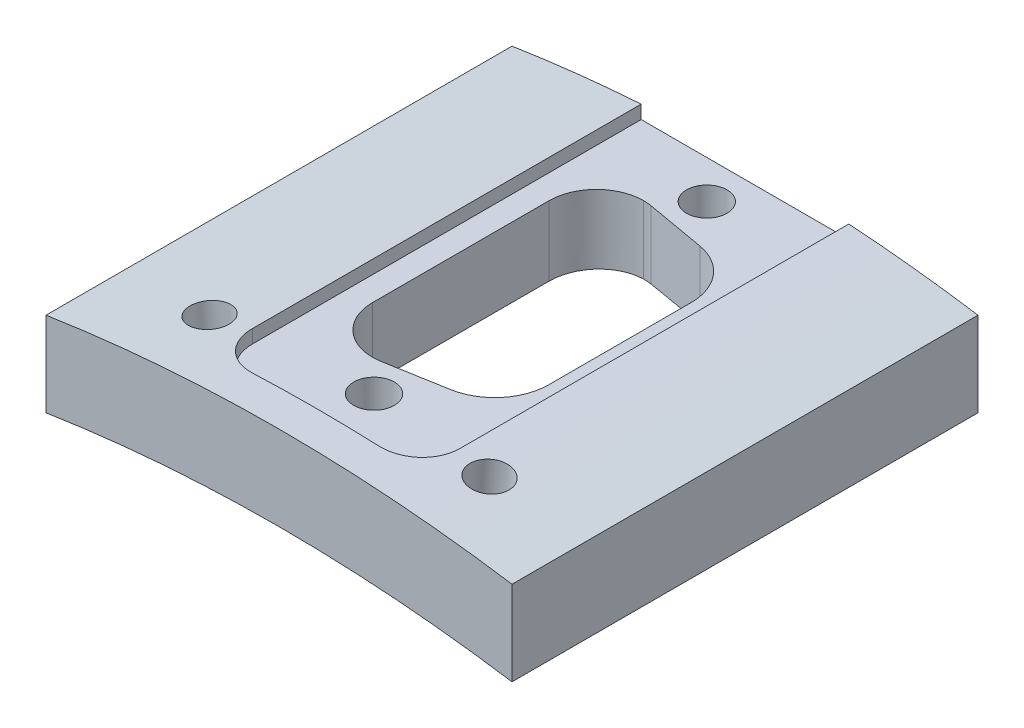
SolidWorks part; units mm, degrees
ref_plane "Front Plane" through (0, 0, 0) normal (0, 0, 1) x (1, 0, 0)
ref_plane "Top Plane" through (0, 0, 0) normal (0, 1, 0) x (1, 0, 0)
ref_plane "Right Plane" through (0, 0, 0) normal (1, 0, 0) x (0, 0, -1)
sketch "Sketch1" plane through (0, 0, 0) normal (0, 0, 1) x (1, 0, 0)
  line L1 (0, 0) -> (-35, 0)
  line L2 (0, 0) -> (0, -12.7)
  line L3 (0, -12.7) -> (-35, -12.7)
  line L4 (-35, 0) -> (-35, -12.7)
  arc A0 (-35, -12.7) -> (0, -12.7) centre (-17.5, -125.7809) cw
  dimension "D1" = 35
  dimension "D3" = 114.427
  dimension "D2" = 12.7
extrude "Boss-Extrude1" add sketch "Sketch1" along normal blind 35 contours L4 A0 L2 L1 region at (-17.5, -5.9076, 0)
ref_plane "Plane2" through (0, -11.3539, 0) normal (0, -1, 0) x (1, 0, 0)
ref_plane "Plane3" through (-1.0808, -12.3533, 0) normal (-0.0872, -0.9962, 0) x (0.9962, -0.0872, 0)
ref_plane "Plane4" through (0.8149, -9.3145, 0) normal (0.0872, -0.9962, 0) x (0.9962, 0.0872, 0)
sketch "Sketch3" plane through (0, 0, 35) normal (0, 0, 1) x (1, 0, 0)
  line L0 (-17.5, -125.6524) -> (-17.5, 0) construction
  line L1 (0, 0) -> (-35, 0) construction
  line L2 (-17.5, -125.6524) -> (-6.5068, 0) construction
  line L3 (-17.5, -125.6524) -> (-28.4932, 0) construction
  circle A0 centre (-17.5, -125.6524) radius 114.3
  dimension "D1" = 228.6
  dimension "D2" = 5
  dimension "D3" = 5
sketch "Sketch6" plane through (-1.0808, -12.3533, 0) normal (-0.0872, -0.9962, 0) x (0.9962, -0.0872, 0)
  line L0 (-6.4821, 35) -> (-6.4821, 0) construction
  line L1 (107.8179, 35) -> (-120.7821, 35) construction
  line L2 (1.1069, 0) -> (-33.7599, 0) construction
  circle A0 centre (-6.4821, 29.7028) radius 1.4732
  dimension "D1" = 2.9464
  dimension "D2" = 29.7028
extrude "Cut-Extrude4" cut sketch "Sketch6" against normal through all and the other way through all
sketch "Sketch7" plane through (0.8149, -9.3145, 0) normal (0.0872, -0.9962, 0) x (0.9962, 0.0872, 0)
  line L0 (-28.3847, 35) -> (-28.3847, 0) construction
  line L1 (85.9153, 35) -> (-142.6847, 35) construction
  line L2 (-1.1069, 0) -> (-35.9737, 0) construction
  circle A0 centre (-28.3847, 29.7028) radius 1.4732
  dimension "D1" = 2.9464
  dimension "D2" = 29.7028
extrude "Cut-Extrude5" cut sketch "Sketch7" against normal through all and the other way through all
sketch "Sketch8" plane through (0, 0, 0) normal (0, 0, -1) x (-1, 0, 0)
  line L0 (0, -6.35) -> (35, -6.35) construction
  line L3 (35, -12.7) -> (35, 0)
  line L4 (35, 0) -> (0, 0)
  line L5 (0, 0) -> (0, -12.7)
  line L6 (35, -12.7) -> (35, 0)
  line L7 (35, 0) -> (0, 0)
  line L8 (0, 0) -> (0, -12.7)
  arc A0 (0, -6.35) -> (35, -6.35) centre (17.5, -119.4309) cw
  arc A1 (35, -12.7) -> (0, -12.7) centre (17.5, -125.7809) ccw
  arc A2 (35, -12.7) -> (0, -12.7) centre (17.5, -125.7809) ccw
  line M6 (35, 0) -> (0, 0)
  line M7 (0, 0) -> (0, -12.7)
  dimension "D3" = 114.427
  dimension "D2" = 6.35
  dimension "D1" = 0
extrude "Cut-Extrude6" cut sketch "Sketch8" against normal through all contours A0 L6 M7 M6 region at (-17.5, -2.7405, 0)
sketch "Sketch9" plane through (0, 0, 0) normal (0, 0, -1) x (-1, 0, 0)
  line L0 (17.5, -11.3539) -> (17.5, -5.0039) construction
  line L2 (35, -12.7) -> (35, -6.35)
  line L3 (0, -6.35) -> (0, -12.7)
  line L4 (35, -12.7) -> (35, -6.35)
  line L5 (0, -6.35) -> (0, -12.7)
  arc A2 (35, -6.35) -> (0, -6.35) centre (17.5, -119.4309) ccw
  arc A3 (35, -12.7) -> (0, -12.7) centre (17.5, -125.7809) ccw
  arc A4 (35, -6.35) -> (0, -6.35) centre (17.5, -119.4309) ccw
  arc A5 (35, -12.7) -> (0, -12.7) centre (17.5, -125.7809) ccw
  dimension "D1" = 0
ref_plane "Plane5" through (-17.5, -5.0039, 0) normal (0, 1, 0) x (-1, 0, 0)
sketch "Sketch10" plane through (-17.5, -5.0039, 0) normal (0, 1, 0) x (-1, 0, 0)
  line L0 (-17.5, 27.8638) -> (17.5, 27.8638) construction
  line L1 (-17.5, 35) -> (-17.5, 0) construction
  line L2 (17.5, 35) -> (17.5, 0) construction
  line L3 (-17.5, 0) -> (17.5, 0) construction
  line L5 (0, 0) -> (0, 27.8638) construction
  line L7 (-17.5, 0) -> (17.5, 0) construction
  line B0 (6.2738, 1.524) -> (6.2738, 29.21)
  line B1 (4.7498, 30.734) -> (-4.7498, 30.734)
  line B2 (-6.2738, 29.21) -> (-6.2738, 1.524)
  line B3 (-4.7498, 0) -> (4.7498, 0)
  line B4 (1.8082, 5.2379) -> (-2.6234, 6.0193)
  line B5 (-5.9817, 10.0215) -> (-5.9817, 20.7125)
  line B6 (-2.6234, 24.7147) -> (1.8082, 25.4961)
  line B7 (5.9817, 21.9942) -> (5.9817, 8.7398)
  circle B8 centre (0, 27.8638) radius 1.524
  arc B9 (4.7498, 0) -> (6.2738, 1.524) centre (4.7498, 1.524) ccw
  arc B10 (6.2738, 29.21) -> (4.7498, 30.734) centre (4.7498, 29.21) ccw
  arc B11 (-4.7498, 30.734) -> (-6.2738, 29.21) centre (-4.7498, 29.21) ccw
  arc B12 (-6.2738, 1.524) -> (-4.7498, 0) centre (-4.7498, 1.524) ccw
  circle B13 centre (0, 2.8702) radius 1.524
  arc B14 (1.8082, 5.2379) -> (2.4257, 5.1838) centre (2.4287, 8.774) ccw
  spline B15 degree 2 poles (5.9817, 8.7398) (5.9815, 8.0613) (5.732, 7.4309) (5.4612, 6.7466) (4.9402, 6.2254) (4.4199, 5.7049) (3.7346, 5.4335) (3.1048, 5.184) (2.4257, 5.1838) knots 0 0 0 0.25 0.25 0.5 0.5 0.75 0.75 1 1 1
  spline B16 degree 2 poles (-2.6234, 6.0193) (-3.3067, 6.14) (-3.911, 6.4799) (-4.5551, 6.8424) (-5.0309, 7.4093) (-5.506, 7.9754) (-5.7516, 8.6735) (-5.9815, 9.3271) (-5.9817, 10.0215) knots 0 0 0 0.25 0.25 0.5 0.5 0.75 0.75 1 1 1
  spline B17 degree 2 poles (-5.9817, 20.7125) (-5.9815, 21.4064) (-5.7516, 22.0605) (-5.5066, 22.7577) (-5.0309, 23.3247) (-4.5559, 23.891) (-3.911, 24.2541) (-3.3072, 24.594) (-2.6234, 24.7147) knots 0 0 0 0.25 0.25 0.5 0.5 0.75 0.75 1 1 1
  spline B18 degree 2 poles (1.8082, 25.4961) (2.1874, 25.5629) (2.5715, 25.5472) (2.9648, 25.5311) (3.3461, 25.429) (3.7263, 25.3272) (4.076, 25.144) (4.4163, 24.9658) (4.7115, 24.7182) (5.0058, 24.4713) (5.2412, 24.1663) (5.4817, 23.8547) (5.6485, 23.497) (5.8149, 23.1402) (5.8994, 22.7547) (5.9816, 22.3797) (5.9817, 21.9942) knots 0 0 0 0.125 0.125 0.25 0.25 0.375 0.375 0.5 0.5 0.625 0.625 0.75 0.75 0.875 0.875 1 1 1
  line B19 (-7.7978, 29.21) -> (-7.7978, 1.524)
  line B20 (-4.7498, -1.524) -> (4.7498, -1.524)
  line B21 (7.7978, 1.524) -> (7.7978, 29.21)
  line B22 (4.7498, 32.258) -> (-4.7498, 32.258)
  arc B23 (-7.7978, 1.524) -> (-4.7498, -1.524) centre (-4.7498, 1.524) ccw
  arc B24 (4.7498, -1.524) -> (7.7978, 1.524) centre (4.7498, 1.524) ccw
  arc B25 (7.7978, 29.21) -> (4.7498, 32.258) centre (4.7498, 29.21) ccw
  arc B26 (-4.7498, 32.258) -> (-7.7978, 29.21) centre (-4.7498, 29.21) ccw
  line B27 (-7.7978, 1.524) -> (-7.7978, -3.2026)
  line B28 (-7.7978, -3.2026) -> (7.7978, -3.2026)
  line B29 (7.7978, -3.2026) -> (7.7978, 1.524)
sketch_block_instance "Block1-2"
sketch_block "Block1" parameters "D1"=1.524
extrude "Cut-Extrude8" cut sketch "Sketch10" against normal blind 1.27 contours B2 B12 B3 B9 B0 B10 B1 B11 B8 B13 B6 B18 B7 B15 B14 B4 B16 B5 B17 | B22 B26 B19 B23 B20 B24 B21 B25 B12 B2 B11 B1 B10 B0 B9 B3 | B18 B6 B17 B5 B16 B4 B14 B15 B7 | B13 | B8 | B24 B20 B23 B27 B28 B29 region at (-23.0927, -5.0039, 0.6811) region at (-17.6541, -5.0039, 15.3679) region at (-17.5, -5.0039, 27.8638) region at (-17.5, -5.0039, 2.8702) region at (-10.858, -5.0039, 31.1022) region at (-17.5, -5.0039, -2.1623)
extrude "Cut-Extrude9" cut sketch "Sketch10<4>" against normal through all contours B18 B6 B17 B5 B16 B4 B14 B15 B7 region at (-17.6541, -5.0039, 15.3679)
sketch "Sketch10<4>" plane through (-17.5, -5.0039, 0) normal (0, 1, 0) x (-1, 0, 0) same geometry as "Sketch10"
extrude "Cut-Extrude10" cut sketch "Sketch10<5>" against normal through all contours B8 | B13 region at (-17.5, -5.0039, 27.8638) region at (-17.5, -5.0039, 2.8702)
sketch "Sketch10<5>" plane through (-17.5, -5.0039, 0) normal (0, 1, 0) x (-1, 0, 0) same geometry as "Sketch10"
